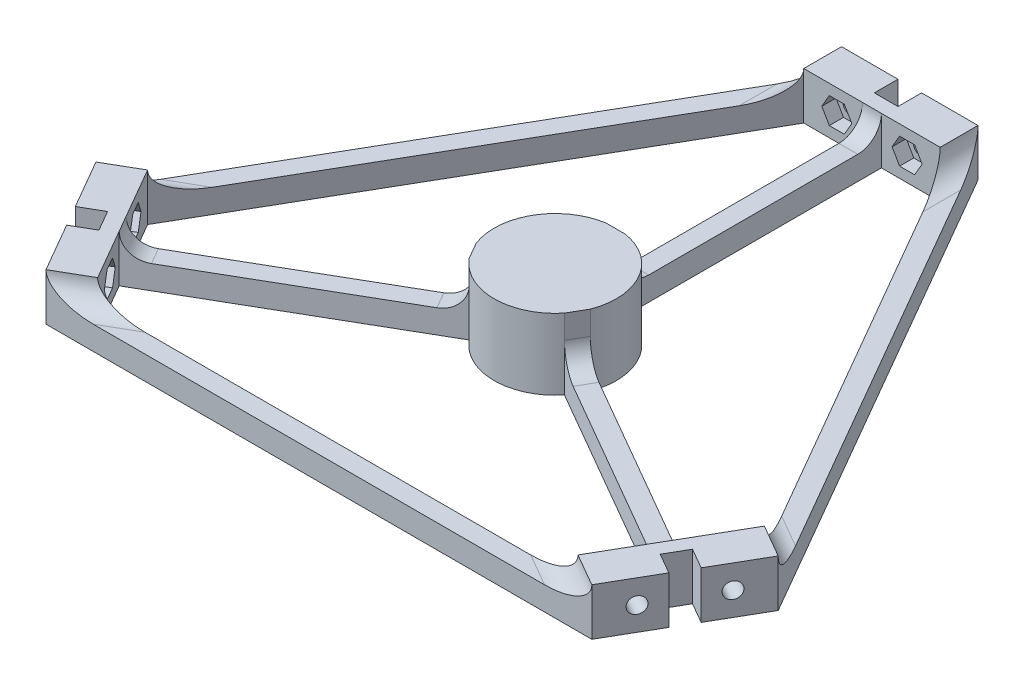
SolidWorks part; units mm, degrees
ref_plane "Front" through (0, 0, 0) normal (0, 0, 1) x (1, 0, 0)
ref_plane "Top" through (0, 0, 0) normal (0, 1, 0) x (1, 0, 0)
ref_plane "Right" through (0, 0, 0) normal (1, 0, 0) x (0, 0, -1)
sketch "Sketch1" plane through (0, 0, 0) normal (0, 1, 0) x (1, 0, 0)
  line L1 (-14.4338, 75) -> (-72.1688, -25)
  line L2 (-57.735, -50) -> (57.735, -50)
  line L3 (72.1688, -25) -> (14.4338, 75)
  line L4 (57.735, -50) -> (72.1688, -25)
  line L5 (14.4338, 75) -> (-14.4338, 75)
  line L6 (-72.1688, -25) -> (-57.735, -50)
  circle A2 centre (0, 0) radius 50 construction
  circle A3 centre (0, 0) radius 75 construction
  dimension "D1" = 100
  dimension "D2" = 150
extrude "Boss-Extrude1" add sketch "Sketch1" along normal blind 15
hole_wizard "M3 Clearance Hole1" positions "3DSketch1" profile "Sketch2" hole size "M3" standard "ANSI Metric"
sketch3d "3DSketch1"
  line L0 (57.735, 0, 50) -> (72.1688, 0, 25) construction
  line L1 (57.735, 15, 50) -> (57.735, 0, 50) construction
  line L2 (72.1688, 15, 25) -> (72.1688, 0, 25) construction
  point P0 (61.235, 5, 43.9378)
  point P2 (68.6688, 5, 31.0622)
  dimension "D1" = 5
  dimension "D2" = 7
  dimension "D3" = 5
  dimension "D4" = 7
sketch "Sketch2" plane through (61.235, 5, 43.9378) normal (0, 1, 0) x (0.5, 0, -0.866)
  line L0 (0, 0) -> (0, 25)
  line L1 (0, 25) -> (1.7, 23.9785)
  line L2 (1.7, 23.9785) -> (1.7, 0)
  line L5 (1.7, 0) -> (0, 0)
  line L10 (0, 25) -> (-1.7, 23.9785) construction
  line L11 (0, -6.35) -> (0, 107.95) construction
  dimension "Hole Dia." = 3.4
  dimension "Hole Depth" = 25
  dimension "Drill Angle" = 118
hole_wizard "M3 Clearance Hole2" positions "3DSketch2" profile "Sketch3" hole size "M3" standard "ANSI Metric"
sketch3d "3DSketch2"
  line L0 (14.4338, 15, -75) -> (14.4338, 0, -75) construction
  line L1 (14.4338, 0, -75) -> (-14.4338, 0, -75) construction
  line L2 (-14.4338, 15, -75) -> (-14.4338, 0, -75) construction
  point P0 (7.4338, 5, -75)
  point P2 (-7.4338, 5, -75)
  dimension "D1" = 7
  dimension "D2" = 5
  dimension "D3" = 5
  dimension "D4" = 7
sketch "Sketch3" plane through (7.4338, 5, -75) normal (1, 0, 0) x (0, 1, 0)
  line L0 (0, 0) -> (0, 25)
  line L1 (0, 25) -> (1.7, 23.9785)
  line L2 (1.7, 23.9785) -> (1.7, 0)
  line L5 (1.7, 0) -> (0, 0)
  line L10 (0, 25) -> (-1.7, 23.9785) construction
  line L11 (0, -6.35) -> (0, 107.95) construction
  dimension "Hole Dia." = 3.4
  dimension "Hole Depth" = 25
  dimension "Drill Angle" = 118
hole_wizard "M3 Clearance Hole3" positions "3DSketch3" profile "Sketch4" hole size "M3" standard "ANSI Metric"
sketch3d "3DSketch3"
  line L0 (-72.1688, 15, 25) -> (-72.1688, 0, 25) construction
  line L1 (-72.1688, 0, 25) -> (-57.735, 0, 50) construction
  line L2 (-57.735, 15, 50) -> (-57.735, 0, 50) construction
  point P0 (-68.6688, 5, 31.0622)
  point P2 (-61.235, 5, 43.9378)
  dimension "D1" = 7
  dimension "D2" = 5
  dimension "D3" = 5
  dimension "D4" = 7
sketch "Sketch4" plane through (-68.6688, 5, 31.0622) normal (0, 1, 0) x (0.5, 0, 0.866)
  line L0 (0, 0) -> (0, 25)
  line L1 (0, 25) -> (1.7, 23.9785)
  line L2 (1.7, 23.9785) -> (1.7, 0)
  line L5 (1.7, 0) -> (0, 0)
  line L10 (0, 25) -> (-1.7, 23.9785) construction
  line L11 (0, -6.35) -> (0, 107.95) construction
  dimension "Hole Dia." = 3.4
  dimension "Hole Depth" = 25
  dimension "Drill Angle" = 118
sketch "Sketch5" plane through (-64.9519, 0, 37.5) normal (-0.866, 0, 0.5) x (0.5, 0, 0.866)
  line L6 (0, 15) -> (0, 0) construction
  line L7 (-14.4338, 15) -> (14.4338, 15) construction
  line L8 (-14.4338, 0) -> (14.4338, 0) construction
  line L10 (-2.5, 15) -> (2.5, 15)
  line L11 (-2.5, 15) -> (-2.5, 0)
  line L12 (-2.5, 0) -> (2.5, 0)
  line L13 (2.5, 15) -> (2.5, 0)
  dimension "D1" = 2.5
  dimension "D2" = 2.5
extrude "Cut-Extrude1" cut sketch "Sketch5" against normal blind 5
sketch "Sketch6" plane through (64.9519, 0, 37.5) normal (0.866, 0, 0.5) x (0.5, 0, -0.866)
  line L0 (0, 15) -> (0, 0) construction
  line L1 (-14.4338, 15) -> (14.4338, 15) construction
  line L2 (-14.4338, 0) -> (14.4338, 0) construction
  line L4 (-2.5, 15) -> (2.5, 15)
  line L5 (-2.5, 15) -> (-2.5, 0)
  line L6 (-2.5, 0) -> (2.5, 0)
  line L7 (2.5, 15) -> (2.5, 0)
  dimension "D1" = 2.5
  dimension "D2" = 2.5
extrude "Cut-Extrude2" cut sketch "Sketch6" against normal blind 5
sketch "Sketch7" plane through (0, 0, -75) normal (0, 0, -1) x (-1, 0, 0)
  line L0 (0, 15) -> (0, 0) construction
  line L1 (-14.4338, 15) -> (14.4338, 15) construction
  line L2 (-14.4338, 0) -> (14.4338, 0) construction
  line L4 (-2.5, 15) -> (2.5, 15)
  line L5 (-2.5, 15) -> (-2.5, 0)
  line L6 (-2.5, 0) -> (2.5, 0)
  line L7 (2.5, 15) -> (2.5, 0)
  dimension "D1" = 2.5
  dimension "D2" = 2.5
extrude "Cut-Extrude3" cut sketch "Sketch7" against normal blind 5
sketch "Sketch8" plane through (0, 15, 0) normal (0, 1, 0) x (1, 0, 0)
  line L0 (65.2406, -21) -> (14.4338, 67)
  line L1 (14.4338, 67) -> (2, 67)
  line L2 (-14.4338, 67) -> (-65.2406, -21)
  line L3 (-65.2406, -21) -> (-59.0237, -31.7679)
  line L4 (-50.8068, -46) -> (50.8068, -46)
  line L5 (50.8068, -46) -> (57.0237, -35.2321)
  line L7 (-14.4338, 75) -> (-72.1688, -25) construction
  line L8 (-2.5, 75) -> (-14.4338, 75) construction
  line L9 (72.1688, -25) -> (14.4338, 75) construction
  line L10 (66.2019, -35.3349) -> (72.1688, -25) construction
  line L11 (-57.735, -50) -> (57.735, -50) construction
  line L12 (-63.7019, -39.6651) -> (-57.735, -50) construction
  line L13 (0, 70) -> (0, -50) construction
  line L14 (-2.5, 70) -> (2.5, 70) construction
  line L15 (60.6218, -35) -> (-43.3013, 25) construction
  line L16 (61.8718, -32.8349) -> (59.3718, -37.1651) construction
  line L17 (-60.6218, -35) -> (43.3013, 25) construction
  line L18 (-59.3718, -37.1651) -> (-61.8718, -32.8349) construction
  line L19 (-59.0237, -31.7679) -> (-12.0711, -4.6599)
  line L20 (-57.0237, -35.2321) -> (-10.0711, -8.124)
  line L21 (2, 67) -> (2, 12.7838)
  line L22 (-2, 67) -> (-2, 12.7838)
  line L23 (59.0237, -31.7679) -> (12.0711, -4.6599)
  line L24 (57.0237, -35.2321) -> (10.0711, -8.124)
  line L25 (59.0237, -31.7679) -> (65.2406, -21)
  line L26 (-2, 67) -> (-14.4338, 67)
  line L27 (-57.0237, -35.2321) -> (-50.8068, -46)
  arc A0 (12.0711, -4.6599) -> (2, 12.7838) centre (0, 0) ccw
  arc A1 (-2, 12.7838) -> (-12.0711, -4.6599) centre (0, 0) ccw
  arc A2 (-10.0711, -8.124) -> (10.0711, -8.124) centre (0, 0) ccw
  dimension "D7" = 2
  dimension "D1" = 4
  dimension "D2" = 4
  dimension "D3" = 4
  dimension "D4" = 8
  dimension "D5" = 8
  dimension "D6" = 8
  dimension "D8" = 2
  dimension "D9" = 2
  dimension "D10" = 2
  dimension "D11" = 2
  dimension "D12" = 2
extrude "Cut-Extrude4" cut sketch "Sketch8" against normal up to next
sketch "Sketch9" plane through (0, 15, 0) normal (0, 1, 0) x (1, 0, 0)
  line L0 (14.4338, 75) -> (14.4338, 67)
  line L1 (14.4338, 67) -> (65.2406, -21)
  line L2 (65.2406, -21) -> (72.1688, -25)
  line L3 (72.1688, -25) -> (14.4338, 75)
  line L4 (57.735, -50) -> (50.8068, -46)
  line L5 (50.8068, -46) -> (-50.8068, -46)
  line L6 (-50.8068, -46) -> (-57.735, -50)
  line L7 (-57.735, -50) -> (57.735, -50)
  line L8 (-14.4338, 75) -> (-14.4338, 67)
  line L9 (-14.4338, 67) -> (-65.2406, -21)
  line L10 (-65.2406, -21) -> (-72.1688, -25)
  line L11 (-72.1688, -25) -> (-14.4338, 75)
  line L12 (-2, 67) -> (2, 67)
  line L13 (2, 67) -> (2, 12.7838)
  line L14 (2, 12.7838) -> (-2, 12.7838)
  line L15 (-2, 12.7838) -> (-2, 67)
  line L16 (-10.0711, -8.124) -> (-57.0237, -35.2321)
  line L17 (-57.0237, -35.2321) -> (-59.0237, -31.7679)
  line L18 (-59.0237, -31.7679) -> (-12.0711, -4.6599)
  line L19 (-12.0711, -4.6599) -> (-10.0711, -8.124)
  line L20 (59.0237, -31.7679) -> (57.0237, -35.2321)
  line L21 (57.0237, -35.2321) -> (10.0711, -8.124)
  line L22 (10.0711, -8.124) -> (12.0711, -4.6599)
  line L23 (12.0711, -4.6599) -> (59.0237, -31.7679)
extrude "Cut-Extrude5" cut sketch "Sketch9" against normal blind 10
fillet "Fillet1" radius 5 12 edges at (11.0711, 5, 6.3919) (58.0237, 5, 33.5) (0, 5, -67) (0, 5, -12.7838) (-68.7047, 5, 23) (-14.4338, 5, -71) (14.4338, 5, -71) (68.7047, 5, 23) (54.2709, 5, 48) (-54.2709, 5, 48) (-58.0237, 5, 33.5) (-11.0711, 5, 6.3919)
sketch "Sketch10" plane through (0, 0, -67) normal (0, 0, 1) x (1, 0, 0)
  line L2 (-10.6092, 5) -> (-9.0215, 2.25)
  line L3 (-9.0215, 2.25) -> (-5.846, 2.25)
  line L4 (-5.846, 2.25) -> (-4.2583, 5)
  line L5 (-4.2583, 5) -> (-5.846, 7.75)
  line L6 (-5.846, 7.75) -> (-9.0215, 7.75)
  line L7 (-9.0215, 7.75) -> (-10.6092, 5)
  circle A0 centre (-7.4338, 5) radius 2.75 construction
  dimension "D1" = 5.5
extrude "Cut-Extrude6" cut sketch "Sketch10" against normal blind 3
sketch "Sketch11" plane through (0, 0, -67) normal (0, 0, 1) x (1, 0, 0)
  line L1 (4.2583, 5) -> (5.846, 2.25)
  line L2 (5.846, 2.25) -> (9.0215, 2.25)
  line L3 (9.0215, 2.25) -> (10.6092, 5)
  line L4 (10.6092, 5) -> (9.0215, 7.75)
  line L5 (9.0215, 7.75) -> (5.846, 7.75)
  line L6 (5.846, 7.75) -> (4.2583, 5)
  circle A0 centre (7.4338, 5) radius 2.75 construction
  dimension "D1" = 5.5
extrude "Cut-Extrude7" cut sketch "Sketch11" against normal blind 3
sketch "Sketch12" plane through (58.0237, 0, 33.5) normal (-0.866, 0, -0.5) x (-0.5, 0, 0.866)
  line L1 (-10.6092, 5) -> (-9.0215, 2.25)
  line L2 (-9.0215, 2.25) -> (-5.846, 2.25)
  line L3 (-5.846, 2.25) -> (-4.2583, 5)
  line L4 (-4.2583, 5) -> (-5.846, 7.75)
  line L5 (-5.846, 7.75) -> (-9.0215, 7.75)
  line L6 (-9.0215, 7.75) -> (-10.6092, 5)
  line L7 (4.2583, 5) -> (5.846, 2.25)
  line L8 (5.846, 2.25) -> (9.0215, 2.25)
  line L9 (9.0215, 2.25) -> (10.6092, 5)
  line L10 (10.6092, 5) -> (9.0215, 7.75)
  line L11 (9.0215, 7.75) -> (5.846, 7.75)
  line L12 (5.846, 7.75) -> (4.2583, 5)
  circle A0 centre (-7.4338, 5) radius 2.75 construction
  circle A1 centre (7.4338, 5) radius 2.75 construction
  dimension "D1" = 5.5
  dimension "D2" = 5.5
extrude "Cut-Extrude8" cut sketch "Sketch12" against normal blind 3
sketch "Sketch13" plane through (-58.0237, 0, 33.5) normal (0.866, 0, -0.5) x (-0.5, 0, -0.866)
  line L1 (-10.6092, 5) -> (-9.0215, 2.25)
  line L2 (-9.0215, 2.25) -> (-5.846, 2.25)
  line L3 (-5.846, 2.25) -> (-4.2583, 5)
  line L4 (-4.2583, 5) -> (-5.846, 7.75)
  line L5 (-5.846, 7.75) -> (-9.0215, 7.75)
  line L6 (-9.0215, 7.75) -> (-10.6092, 5)
  line L7 (4.2583, 5) -> (5.846, 2.25)
  line L8 (5.846, 2.25) -> (9.0215, 2.25)
  line L9 (9.0215, 2.25) -> (10.6092, 5)
  line L10 (10.6092, 5) -> (9.0215, 7.75)
  line L11 (9.0215, 7.75) -> (5.846, 7.75)
  line L12 (5.846, 7.75) -> (4.2583, 5)
  circle A0 centre (-7.4338, 5) radius 2.75 construction
  circle A1 centre (7.4338, 5) radius 2.75 construction
  dimension "D1" = 5.5
  dimension "D2" = 5.5
extrude "Cut-Extrude9" cut sketch "Sketch13" against normal blind 3
sketch "Sketch14" plane through (0, 15, 0) normal (0, 1, 0) x (1, 0, 0)
  line L0 (-72.1688, -25) -> (-65.2406, -21)
  line L1 (-65.2406, -21) -> (-50.8068, -46)
  line L2 (-50.8068, -46) -> (-57.735, -50)
  line L3 (-57.735, -50) -> (-72.1688, -25)
  line L4 (-14.4338, 75) -> (-14.4338, 67)
  line L5 (-14.4338, 67) -> (14.4338, 67)
  line L6 (14.4338, 67) -> (14.4338, 75)
  line L7 (14.4338, 75) -> (-14.4338, 75)
  line L8 (65.2406, -21) -> (72.1688, -25)
  line L9 (72.1688, -25) -> (57.735, -50)
  line L10 (57.735, -50) -> (50.8068, -46)
  line L11 (57.735, -50) -> (50.8068, -46) construction
  line L12 (50.8068, -46) -> (65.2406, -21) construction
  line L13 (50.8068, -46) -> (65.2406, -21)
extrude "Cut-Extrude10" cut sketch "Sketch14" against normal up to vertex (5 mm away) up to point (-57.735, 10, 50)
sketch "Sketch15" plane through (0, 0, 0) normal (0, -1, 0) x (-1, 0, 0)
  circle A0 centre (0, 0) radius 10
  dimension "D1" = 20
extrude "Cut-Extrude11" cut sketch "Sketch15" against normal blind 12
